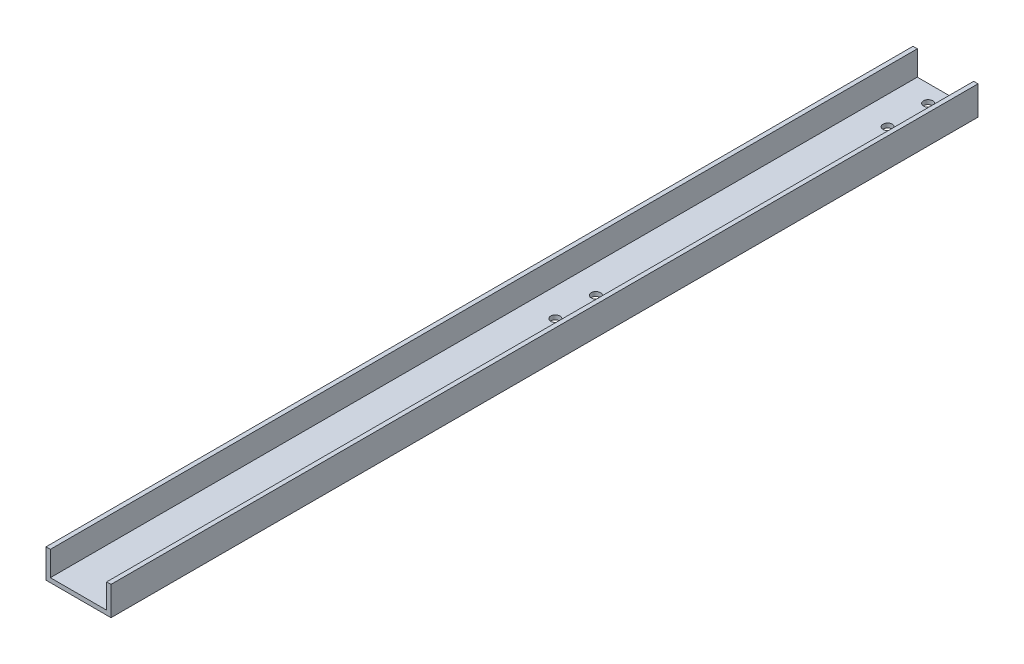
SolidWorks part; units mm, degrees
material "1060-H18 Barre (SS)"
ref_plane "Plan de face" through (0, 0, 0) normal (0, 0, 1) x (1, 0, 0)
ref_plane "Plan de dessus" through (0, 0, 0) normal (0, 1, 0) x (1, 0, 0)
ref_plane "Plan de droite" through (0, 0, 0) normal (1, 0, 0) x (0, 0, -1)
sketch "Esquisse1" plane through (0, 0, 0) normal (0, 0, 1) x (1, 0, 0)
  line L0 (-11.25, 0) -> (11.25, 0)
  line L1 (11.25, 0) -> (11.25, 10)
  line L2 (11.25, 10) -> (9.75, 10)
  line L3 (9.75, 10) -> (9.75, 1.5)
  line L4 (9.75, 1.5) -> (-9.75, 1.5)
  line L5 (-9.75, 1.5) -> (-9.75, 10)
  line L6 (-9.75, 10) -> (-11.25, 10)
  line L7 (-11.25, 10) -> (-11.25, 0)
  line L8 (0, 0) -> (0, 15.264) construction
  dimension "D1" = 1.5
  dimension "D2" = 1.5
  dimension "D3" = 10
  dimension "D4" = 22.5
extrude "Boss.-Extru.1" add sketch "Esquisse1" along normal blind 300
sketch "Esquisse2" plane through (0, 0, 0) normal (0, -1, 0) x (1, 0, 0)
  line L0 (0, 0) -> (0, 26.1584) construction
  line L1 (-11.25, 0) -> (11.25, 0) construction
  circle A0 centre (0, 6) radius 1.6
  circle A1 centre (0, 20) radius 1.6
  dimension "D1" = 3.2
  dimension "D2" = 3.2
  dimension "D3" = 14
  dimension "D4" = 6
extrude "Enlèv. mat.-Extru.1" cut sketch "Esquisse2" against normal through all
pattern_linear "Répétition linéaire1" count 2 spacing 115 along (0, 0, 1) of "Enlèv. mat.-Extru.1"
